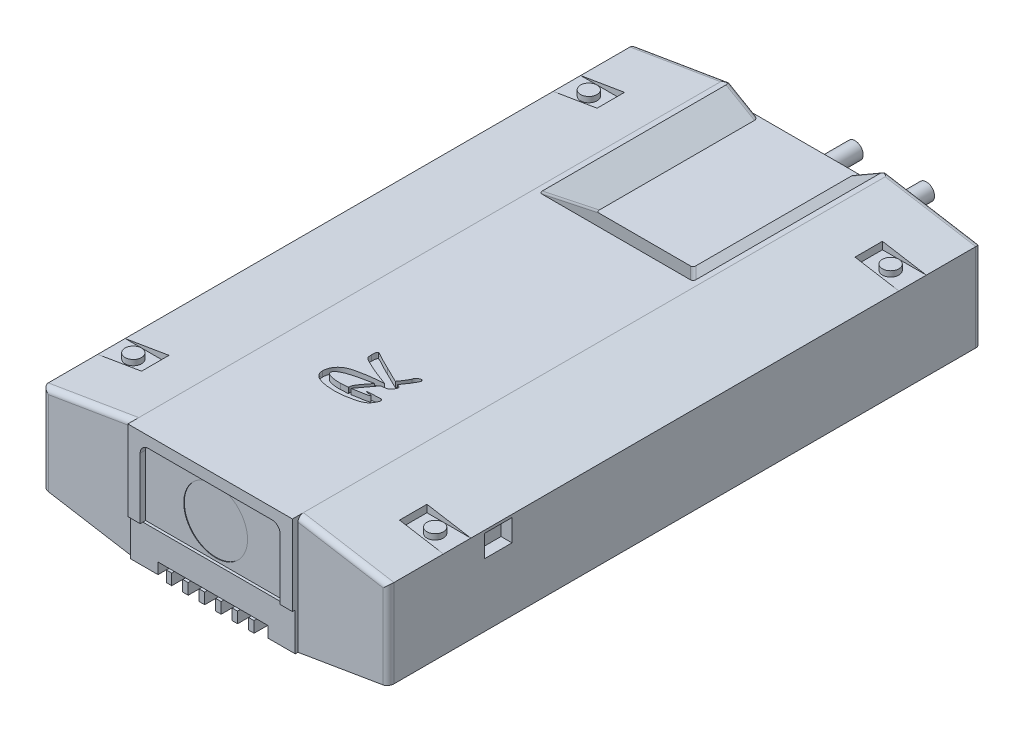
SolidWorks part; units mm, degrees
ref_plane "前视基准面" through (0, 0, 0) normal (0, 0, 1) x (1, 0, 0)
ref_plane "上视基准面" through (0, 0, 0) normal (0, 1, 0) x (1, 0, 0)
ref_plane "右视基准面" through (0, 0, 0) normal (1, 0, 0) x (0, 0, -1)
sketch "草图1" plane through (0, 0, 0) normal (0, 0, 1) x (1, 0, 0)
  line L0 (-15, 10.77) -> (-31.5, 8)
  line L1 (15, -10.77) -> (-15, -10.77)
  line L2 (15, -10.77) -> (15, 10.77) construction
  line L3 (15, 10.77) -> (-15, 10.77)
  line L4 (-15, -10.77) -> (-15, 10.77) construction
  line L5 (15, -10.77) -> (-15, 10.77) construction
  line L6 (15, 10.77) -> (-15, -10.77) construction
  line L7 (31.5, -8) -> (-31.5, -8) construction
  line L8 (31.5, -8) -> (31.5, 8)
  line L9 (31.5, 8) -> (-31.5, 8) construction
  line L10 (-31.5, -8) -> (-31.5, 8)
  line L11 (31.5, -8) -> (-31.5, 8) construction
  line L12 (31.5, 8) -> (-31.5, -8) construction
  line L13 (-31.5, -8) -> (-15, -10.77)
  line L14 (15, -10.77) -> (31.5, -8)
  line L15 (31.5, 8) -> (15, 10.77)
  point P0 (0, 0)
  point P6 (0, 0)
  dimension "D1" = 30
  dimension "D2" = 21.54
  dimension "D3" = 63
  dimension "D4" = 16
extrude "凸台-拉伸1" add sketch "草图1" along normal blind 109
sketch "草图2" plane through (0, 0, 109) normal (0, 0, 1) x (1, 0, 0)
  line L0 (-15, -10.77) -> (15, -10.77) construction
  line L1 (10, -12.77) -> (-10, -12.77)
  line L2 (10, -12.77) -> (10, -8.77)
  line L3 (10, -8.77) -> (-10, -8.77)
  line L4 (-10, -12.77) -> (-10, -8.77)
  line L5 (10, -12.77) -> (-10, -8.77) construction
  line L6 (10, -8.77) -> (-10, -12.77) construction
  point P0 (0, -10.77)
  dimension "D1" = 20
  dimension "D2" = 4
extrude "切除-拉伸1" cut sketch "草图2" against normal up to surface (109 mm away) up to face at (0, 0, 0)
sketch "草图5" plane through (0, 0, 0) normal (0, 0, -1) x (-1, 0, 0)
  line L0 (0, 0) -> (0, -8.77) construction
  line L1 (-10, -8.77) -> (10, -8.77) construction
  circle A0 centre (-6.5, -3.77) radius 3
  circle A1 centre (6.5, -3.77) radius 3
  dimension "D1" = 13
  dimension "D2" = 6
  dimension "D3" = 5
extrude "凸台-拉伸2" add sketch "草图5" along normal blind 5
sketch "草图6" plane through (0, 0, -5) normal (0, 0, -1) x (-1, 0, 0)
  line L0 (0, 0) -> (0, -8.77) construction
  line L1 (-10, -8.77) -> (10, -8.77) construction
  circle A0 centre (-6.5, -3.77) radius 1.5
  circle A1 centre (6.5, -3.77) radius 1.5
  dimension "D1" = 3
extrude "凸台-拉伸3" add sketch "草图6" along normal blind 10
sketch "草图7" plane through (0, 10.77, 0) normal (0, 1, 0) x (1, 0, 0)
  line L0 (0, 0) -> (0, -10) construction
  line L2 (14, -35) -> (-14, -35)
  line L3 (14, -35) -> (14, 15)
  line L4 (14, 15) -> (-14, 15)
  line L5 (-14, -35) -> (-14, 15)
  line L6 (14, -35) -> (-14, 15) construction
  line L7 (14, 15) -> (-14, -35) construction
  dimension "D1" = 10
  dimension "D2" = 28
  dimension "D3" = 50
extrude "切除-拉伸3" cut sketch "草图7" against normal blind 3 draft 60
sketch "草图8" plane through (0, 10.77, 0) normal (0, 1, 0) x (1, 0, 0)
  line L0 (-6.2607, -86.2805) -> (4.9162, -86.2805) construction
  text T0 "<r180>R</r>" font "华文行楷" height 10
extrude "切除-拉伸4" cut sketch "草图8" against normal blind 1
sketch "草图9" plane through (0, 0, 109) normal (0, 0, 1) x (1, 0, 0)
  line L1 (-15, -10.77) -> (15, -10.77)
  line L2 (-15, -10.77) -> (-15, 10.77)
  line L3 (-15, 10.77) -> (15, 10.77)
  line L4 (15, -10.77) -> (15, 10.77)
  dimension "D1" = 21.54
extrude "切除-拉伸5" cut sketch "草图9" against normal blind 1 flip side to cut
sketch "草图10" plane through (0, 0, 109) normal (0, 0, 1) x (1, 0, 0)
  line L0 (-15, 10.77) -> (-15, -10.77) construction
  line L2 (-15, -3.8503) -> (15, -3.8503)
  line L3 (-15, -3.8503) -> (-15, -10.77)
  line L4 (-15, -10.77) -> (15, -10.77)
  line L5 (15, -3.8503) -> (15, -10.77)
  line L6 (0, 0) -> (0, 8.77) construction
  line L7 (-12.7571, -3.8503) -> (12.7571, -3.8503)
  line L8 (-12.7571, -3.8503) -> (-12.7571, 7.27)
  line L9 (-11.2571, 8.77) -> (11.2571, 8.77)
  line L10 (12.7571, -3.8503) -> (12.7571, 7.27)
  line L11 (15, 10.77) -> (-15, 10.77) construction
  arc A0 (-12.7571, 7.27) -> (-11.2571, 8.77) centre (-11.2571, 7.27) cw
  arc A1 (11.2571, 8.77) -> (12.7571, 7.27) centre (11.2571, 7.27) cw
  line M1 (-15, 10.77) -> (-15, -10.77)
  line M2 (-15, -10.77) -> (-10, -10.77)
  line M3 (-10, -10.77) -> (-10, -8.77)
  line M4 (-10, -8.77) -> (10, -8.77)
  line M5 (10, -8.77) -> (10, -10.77)
  line M6 (10, -10.77) -> (15, -10.77)
  line M7 (15, -10.77) -> (15, 10.77)
  dimension "D1" = 1.5
  dimension "D2" = 2
extrude "切除-拉伸6" cut sketch "草图10" against normal blind 1 contours A1 L9 A0 L8 L2 L10 | L2 M1 M2 M3 M4 M5 M6 M7 region at (0, -6.723, 109) region at (0, 2.4419, 109)
sketch "草图23" plane through (0, 0, 108) normal (0, 0, 1) x (1, 0, 0)
  line L0 (12.7571, -3.8503) -> (15, -3.8503) construction
  line L1 (-15, -10.77) -> (15, -10.77)
  line L2 (-15, -10.77) -> (-15, -3.8503)
  line L3 (-15, -3.8503) -> (15, -3.8503)
  line L4 (15, -10.77) -> (15, -3.8503)
  line L5 (12.7571, -3.8503) -> (15, -3.8503) construction
  line L7 (-10, -8.77) -> (10, -8.77)
  line L8 (-10, -8.77) -> (-10, -10.77)
  line L9 (-10, -10.77) -> (10, -10.77)
  line L10 (10, -8.77) -> (10, -10.77)
  line M2 (-15, -10.77) -> (-10, -10.77)
  line M3 (-10, -10.77) -> (-10, -8.77)
  line M4 (-10, -8.77) -> (10, -8.77)
  line M5 (10, -8.77) -> (10, -10.77)
  line M6 (10, -10.77) -> (15, -10.77)
  line M13 (-12.7571, -3.8503) -> (-15, -3.8503)
  line M17 (15, -3.8503) -> (12.7571, -3.8503)
extrude "凸台-拉伸7" add sketch "草图23" along normal blind 0.5 contours L4 L3 L2 M6 M17 M13 M2 M3 M4 M5 region at (0, -6.723, 108)
sketch "草图11" plane through (0, 10.77, 0) normal (0, 1, 0) x (1, 0, 0)
  line L0 (-31.5, -54) -> (31.5, -54) construction
  line L1 (-31.5, -108) -> (-31.5, 0) construction
  line L2 (31.5, -108) -> (31.5, 0) construction
  line L3 (-15, -108) -> (-31.5, -108) construction
  line L4 (-31.5, -98) -> (-23.5, -98)
  line L5 (-31.5, -98) -> (-31.5, -93)
  line L6 (-31.5, -93) -> (-23.5, -93)
  line L7 (-23.5, -98) -> (-23.5, -93)
  line L8 (-23.5, -10) -> (-23.5, -15)
  line L9 (-31.5, -15) -> (-23.5, -15)
  line L10 (-31.5, -10) -> (-31.5, -15)
  line L11 (-31.5, -10) -> (-23.5, -10)
  line L12 (0, -115.3983) -> (0, 13.4854) construction
  line L13 (23.5, -10) -> (23.5, -15)
  line L14 (31.5, -10) -> (23.5, -10)
  line L15 (31.5, -10) -> (31.5, -15)
  line L16 (31.5, -15) -> (23.5, -15)
  line L17 (23.5, -98) -> (23.5, -93)
  line L18 (31.5, -93) -> (23.5, -93)
  line L19 (31.5, -98) -> (31.5, -93)
  line L20 (31.5, -98) -> (23.5, -98)
  dimension "D1" = 5
  dimension "D2" = 8
  dimension "D3" = 10
extrude "切除-拉伸7" cut sketch "草图11" against normal up to vertex (2.77 mm away) up to point (-31.5, 8, 0)
sketch "草图25" plane through (0, 0, 108) normal (0, 0, 1) x (1, 0, 0)
  line L0 (12.7571, -3.8503) -> (-12.7571, -3.8503) construction
  line L1 (-11.2571, 8.77) -> (11.2571, 8.77) construction
  line L2 (0, 2.4598) -> (0, 0)
  circle A0 centre (0, 2.4598) radius 6.3102 construction
  circle A1 centre (0, 2.4598) radius 5.8102
  dimension "D1" = 0.5
extrude "切除-拉伸12" cut sketch "草图25" against normal blind 0.1 contours A1 region at (-5.6458, 2.4598, 108)
sketch "草图13" plane through (31.5, 0, 0) normal (1, 0, 0) x (0, 0, -1)
  line L0 (-108, 5.5) -> (-88, 5.5) construction
  line L1 (-108, -8) -> (-108, 8) construction
  line L3 (-90.5, 3.5) -> (-85.5, 3.5)
  line L4 (-90.5, 3.5) -> (-90.5, 7.5)
  line L5 (-90.5, 7.5) -> (-85.5, 7.5)
  line L6 (-85.5, 3.5) -> (-85.5, 7.5)
  line L7 (-90.5, 3.5) -> (-85.5, 7.5) construction
  line L8 (-90.5, 7.5) -> (-85.5, 3.5) construction
  line L9 (-93, 8) -> (-15, 8) construction
  dimension "D1" = 5
  dimension "D2" = 4
  dimension "D3" = 20
  dimension "D4" = 0.5
extrude "切除-拉伸9" cut sketch "草图13" against normal blind 2
mirror "镜向1" about plane through (0, 0, 0) normal (1, 0, 0) of "切除-拉伸9"
sketch "草图15" plane through (0, 0, 109) normal (0, 0, 1) x (1, 0, 0)
  line L0 (-10, -10.77) -> (10, -10.77) construction
  line L1 (10, -8.77) -> (-10, -8.77) construction
  line L2 (-8, -8.77) -> (-7, -8.77)
  line L3 (-8, -8.77) -> (-8, -10.77)
  line L4 (-8, -10.77) -> (-7, -10.77)
  line L5 (-7, -8.77) -> (-7, -10.77)
  line L6 (-10, -8.77) -> (-10, -10.77) construction
  line L7 (-5, -8.77) -> (-4, -8.77)
  line L8 (-5, -8.77) -> (-5, -10.77)
  line L9 (-5, -10.77) -> (-4, -10.77)
  line L10 (-4, -8.77) -> (-4, -10.77)
  line L11 (-2, -8.77) -> (-1, -8.77)
  line L12 (-2, -8.77) -> (-2, -10.77)
  line L13 (-2, -10.77) -> (-1, -10.77)
  line L14 (-1, -8.77) -> (-1, -10.77)
  line L15 (0, -8.77) -> (0, -10.77) construction
  line L16 (2, -10.77) -> (1, -10.77)
  line L17 (5, -10.77) -> (4, -10.77)
  line L18 (8, -10.77) -> (7, -10.77)
  line L19 (8, -8.77) -> (7, -8.77)
  line L20 (5, -8.77) -> (4, -8.77)
  line L21 (2, -8.77) -> (1, -8.77)
  line L22 (1, -8.77) -> (1, -10.77)
  line L23 (2, -8.77) -> (2, -10.77)
  line L24 (4, -8.77) -> (4, -10.77)
  line L25 (5, -8.77) -> (5, -10.77)
  line L26 (7, -8.77) -> (7, -10.77)
  line L27 (8, -8.77) -> (8, -10.77)
  dimension "D1" = 2
  dimension "D2" = 1
  dimension "D3" = 2
  dimension "D4" = 1
  dimension "D5" = 2
  dimension "D6" = 1
extrude "凸台-拉伸4" add sketch "草图15" against normal up to surface (109 mm away) up to face at (0, -0.125, 0)
sketch "草图16" plane through (0, 8, 0) normal (0, 1, 0) x (1, 0, 0)
  line L0 (-31.5, -95.5) -> (-27.5, -95.5) construction
  line L1 (-31.5, -93) -> (-31.5, -98) construction
  line L2 (-31.5, -54) -> (31.5, -54) construction
  line L3 (-31.5, -93) -> (-31.5, -15) construction
  line L4 (31.5, -93) -> (31.5, -15) construction
  line L5 (0, -107.6011) -> (0, 11.3021) construction
  circle A0 centre (-27.5, -95.5) radius 1.5
  circle A1 centre (-27.5, -12.5) radius 1.5
  circle A2 centre (27.5, -95.5) radius 1.5
  circle A3 centre (27.5, -12.5) radius 1.5
  dimension "D1" = 3
  dimension "D2" = 4
extrude "凸台-拉伸5" add sketch "草图16" along normal blind 1
fillet "圆角1" radius 1 12 edges at (31.5, 0, 108) (31.5, 0, 0) (-31.5, 0, 0) (-23.25, 9.385, 0) (-11.4019, 9.27, 0) (-11.4019, 9.27, 32.4019) (11.4019, 9.27, 32.4019) (11.4019, 9.27, 0) (23.25, 9.385, 0) (23.25, 9.385, 108) (-23.25, 9.385, 108) (-31.5, 0, 108)
sketch "草图20" plane through (0, -10.77, 0) normal (0, -1, 0) x (1, 0, 0)
  line L0 (-15, 47.5) -> (15, 47.5) construction
  line L1 (-15, 108) -> (-15, 0) construction
  line L2 (15, 108) -> (15, 0) construction
  line L3 (0, 47.5) -> (0, 104.6727) construction
  line L5 (10, 0) -> (15, 0) construction
  circle A0 centre (-7, 87.5) radius 3.5
  circle A1 centre (-7, 7.5) radius 3.5
  circle A2 centre (7, 7.5) radius 3.5
  circle A3 centre (7, 87.5) radius 3.5
  point P21 (12.5, 0)
  dimension "D1" = 7
  dimension "D2" = 14
  dimension "D3" = 80
  dimension "D4" = 7.5
sketch "草图22" plane through (0, -10.77, 0) normal (0, -1, 0) x (1, 0, 0)
  line L1 (-10.0311, 89.25) -> (-3.9689, 89.25)
  line L2 (-10.0311, 89.25) -> (-10.0311, 85.75)
  line L3 (-10.0311, 85.75) -> (-3.9689, 85.75)
  line L4 (-3.9689, 89.25) -> (-3.9689, 85.75)
  line L5 (-10.0311, 89.25) -> (-3.9689, 85.75) construction
  line L6 (-10.0311, 85.75) -> (-3.9689, 89.25) construction
  line L10 (-15, 47.5) -> (15, 47.5) construction
  line L11 (-15, 47.5) -> (15, 47.5) construction
  line L12 (0, 47.5) -> (0, 104.6727) construction
  line L13 (0, -9.6727) -> (0, 104.6727) construction
  line L14 (10.0311, 85.75) -> (3.9689, 89.25) construction
  line L15 (10.0311, 89.25) -> (3.9689, 85.75) construction
  line L16 (3.9689, 89.25) -> (3.9689, 85.75)
  line L17 (10.0311, 85.75) -> (3.9689, 85.75)
  line L18 (10.0311, 89.25) -> (10.0311, 85.75)
  line L19 (10.0311, 89.25) -> (3.9689, 89.25)
  line L20 (10.0311, 5.75) -> (3.9689, 9.25) construction
  line L21 (10.0311, 9.25) -> (3.9689, 5.75) construction
  line L22 (-10.0311, 9.25) -> (-3.9689, 5.75) construction
  line L23 (-10.0311, 5.75) -> (-3.9689, 9.25) construction
  line L24 (10.0311, 5.75) -> (3.9689, 5.75)
  line L25 (10.0311, 5.75) -> (10.0311, 9.25)
  line L26 (10.0311, 9.25) -> (3.9689, 9.25)
  line L27 (3.9689, 5.75) -> (3.9689, 9.25)
  line L28 (-3.9689, 5.75) -> (-3.9689, 9.25)
  line L29 (-10.0311, 9.25) -> (-3.9689, 9.25)
  line L30 (-10.0311, 5.75) -> (-10.0311, 9.25)
  line L31 (-10.0311, 5.75) -> (-3.9689, 5.75)
  circle A0 centre (-7, 87.5) radius 3.5 construction
  point P0 (-7, 87.5)
  point P12 (7, 87.5)
  point P24 (7, 7.5)
  point P25 (-7, 7.5)
  dimension "D1" = 3.5
extrude "凸台-拉伸6" add sketch "草图22" against normal up to surface (2 mm away) up to face at (-6, -8.77, 54.25)
hole_wizard "M2 螺纹孔1" positions "3D草图1" profile "草图21" tap size "M2" standard "GB"
sketch3d "3D草图1"
  point P0 (-7, -10.77, 87.5)
  point P3 (7, -10.77, 87.5)
  point P6 (-7, -10.77, 7.5)
  point P9 (7, -10.77, 7.5)
sketch "草图21" plane through (-7, -10.77, 87.5) normal (1, 0, 0) x (0, 0, -1)
  line L0 (0, 0) -> (0, 4.4807)
  line L1 (0, 4.4807) -> (0.8, 4)
  line L2 (0.8, 4) -> (0.8, 0)
  line L5 (0.8, 0) -> (0, 0)
  line L10 (0, 4.4807) -> (-0.8, 4) construction
  line L11 (0, -6.35) -> (0, 107.95) construction
  dimension "螺纹孔钻头直径" = 1.6
  dimension "螺纹孔钻头深度" = 4
  dimension "导头角度" = 118
cosmetic thread "孔螺蚊线1" parameters "D1"=4, "D2"=2
cosmetic thread "孔螺蚊线2" parameters "D1"=4, "D2"=2
cosmetic thread "孔螺蚊线3" parameters "D1"=4, "D2"=2
cosmetic thread "孔螺蚊线4" parameters "D1"=4, "D2"=2
